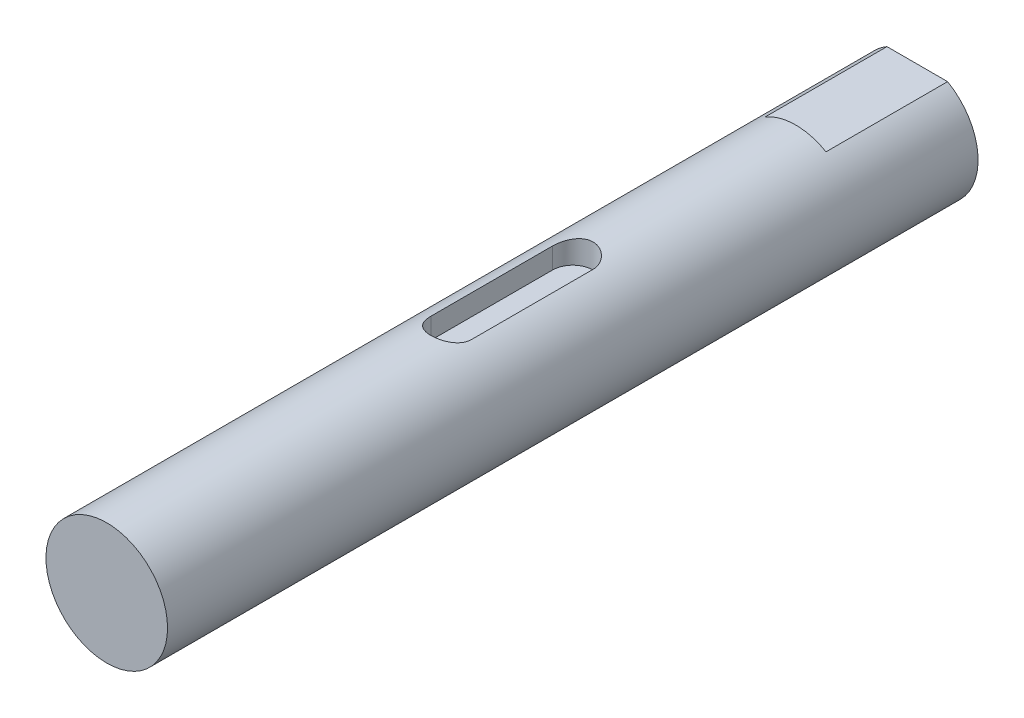
SolidWorks part; units mm, degrees
material "Plain Carbon Steel"
ref_plane "Front Plane" through (0, 0, 0) normal (0, 0, 1) x (1, 0, 0)
ref_plane "Top Plane" through (0, 0, 0) normal (0, 1, 0) x (1, 0, 0)
ref_plane "Right Plane" through (0, 0, 0) normal (1, 0, 0) x (0, 0, -1)
sketch "Sketch1" plane through (0, 0, 0) normal (0, 0, 1) x (1, 0, 0)
  circle A0 centre (0, 0) radius 7.5
  dimension "D1" = 15
extrude "Boss-Extrude1" add sketch "Sketch1" along normal mid plane 100
sketch "Sketch2" plane through (0, 0, 0) normal (0, 0, 1) x (1, 0, 0)
  line L0 (0, 0) -> (0, 7.5) construction
  line L1 (-2.5, 4.5) -> (2.5, 4.5)
  line L2 (-2.5, 4.5) -> (-2.5, 9.5)
  line L3 (-2.5, 9.5) -> (2.5, 9.5)
  line L4 (2.5, 4.5) -> (2.5, 9.5)
  circle A0 centre (0, 0) radius 7.5 construction
  dimension "D1" = 5
  dimension "D2" = 3
  dimension "D3" = 5
extrude "Cut-Extrude1" cut sketch "Sketch2" against normal mid plane 20
fillet "Fillet1" 2 edges at (-2.5, 5.7855, -10) (2.5, 5.7855, -10) type full round first side face at (-2.5, 5.7855, 0) second side face at (2.5, 5.7855, 0) middle face at (0, 5.8928, -10)
fillet "Fillet2" 2 edges at (-2.5, 5.7855, 10) (2.5, 5.7855, 10) type full round first side face at (-2.5, 5.7855, 1.25) second side face at (2.5, 5.7855, 1.25) middle face at (0, 5.8928, 10)
sketch "Sketch3" plane through (0, 0, -50) normal (0, 0, -1) x (-1, 0, 0)
  line L0 (-3.7417, 6.5) -> (3.7417, 6.5)
  line L1 (6.5, -3.7417) -> (6.5, 3.7417)
  circle A0 centre (0, 0) radius 7.5 construction
  arc A1 (6.5, -3.7417) -> (6.5, 3.7417) centre (0, 0) ccw
  arc A2 (3.7417, 6.5) -> (-3.7417, 6.5) centre (0, 0) ccw
  point P6 (6.5, 0)
  point P7 (0, 6.5)
  dimension "D1" = 1
extrude "Cut-Extrude2" cut sketch "Sketch3" against normal blind 15
